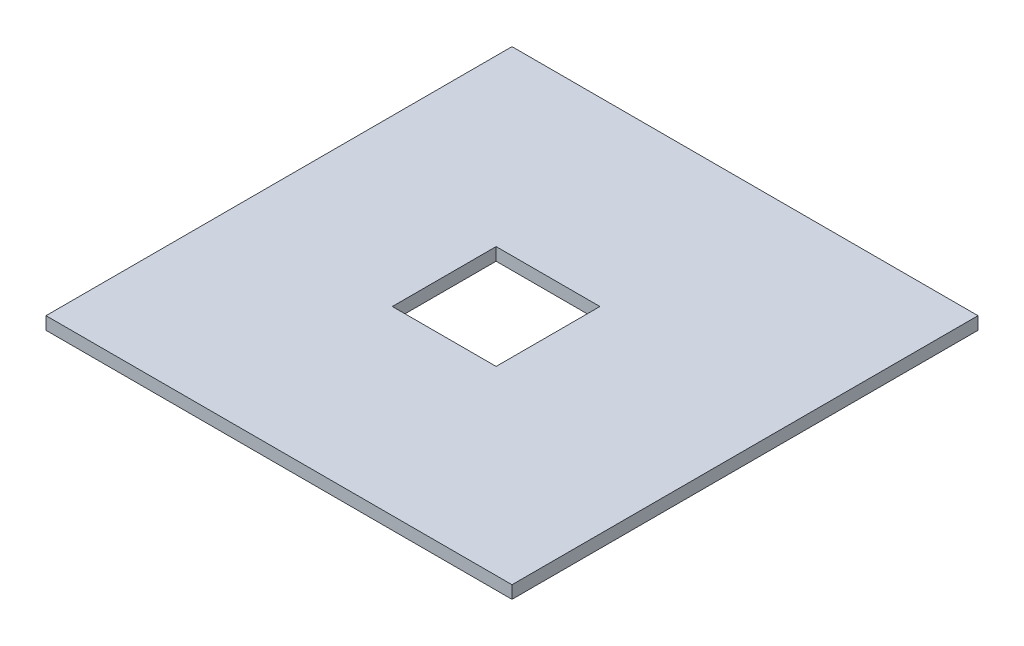
SolidWorks part; units mm, degrees
material "Acrylic (Medium-high impact)"
ref_plane "Front Plane" through (0, 0, 0) normal (0, 0, 1) x (1, 0, 0)
ref_plane "Top Plane" through (0, 0, 0) normal (0, 1, 0) x (1, 0, 0)
ref_plane "Right Plane" through (0, 0, 0) normal (1, 0, 0) x (0, 0, -1)
sketch "Sketch2" plane through (0, 0, 0) normal (0, 1, 0) x (1, 0, 0)
  line L11 (-714.2229, -7.6601) -> (-494.2229, -7.6601)
  line L12 (-714.2229, -7.6601) -> (-714.2229, 212.3399)
  line L13 (-714.2229, 212.3399) -> (-494.2229, 212.3399)
  line L14 (-494.2229, -7.6601) -> (-494.2229, 212.3399)
  dimension "D1" = 220
  dimension "D2" = 220
extrude "Boss-Extrude1" add sketch "Sketch2" along normal blind 6
sketch "Sketch3" plane through (0, 6, 0) normal (0, 1, 0) x (1, 0, 0)
  line L1 (-587.2229, 126.8399) -> (-636.2229, 126.8399)
  line L2 (-587.2229, 126.8399) -> (-587.2229, 77.8399)
  line L3 (-587.2229, 77.8399) -> (-636.2229, 77.8399)
  line L4 (-636.2229, 126.8399) -> (-636.2229, 77.8399)
  dimension "D1" = 0
  dimension "D2" = 0
  dimension "D3" = 0
extrude "Cut-Extrude1" cut sketch "Sketch3" against normal blind 10
